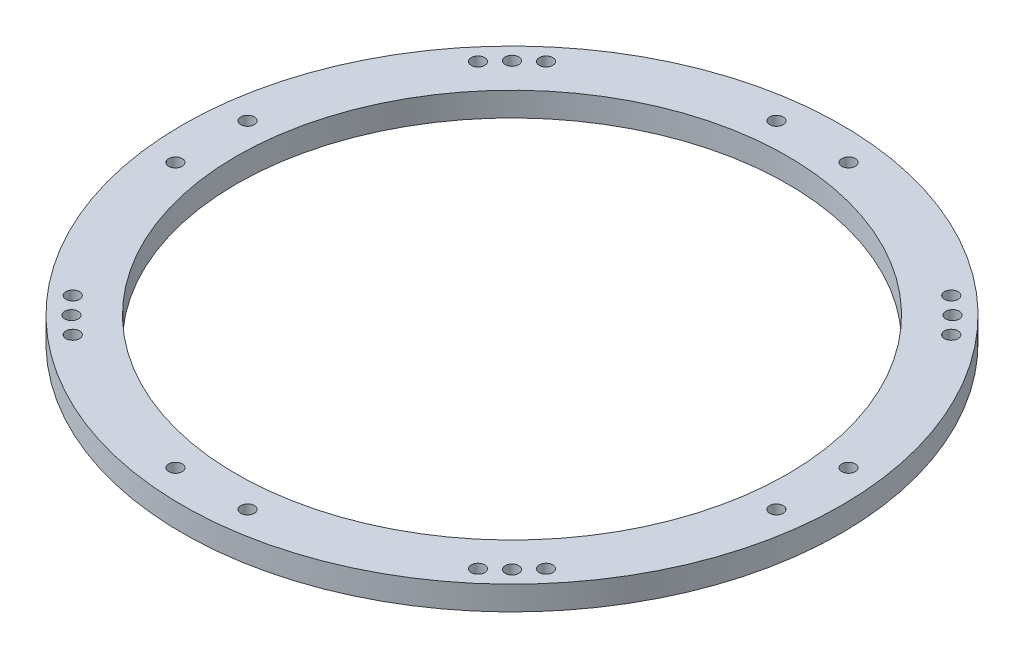
SolidWorks part; units mm, degrees
material "Oak"
ref_plane "Front Plane" through (0, 0, 0) normal (0, 0, 1) x (1, 0, 0)
ref_plane "Top Plane" through (0, 0, 0) normal (0, 1, 0) x (1, 0, 0)
ref_plane "Right Plane" through (0, 0, 0) normal (1, 0, 0) x (0, 0, -1)
sketch "Sketch1" plane through (0, 0, 0) normal (0, 0, 1) x (1, 0, 0)
  line L0 (0, -200000) -> (0, 218797.9879) construction
  line L5 (0, -200000) -> (0, 218797.9879) construction
  line L6 (174.1012, 207.3685) -> (174.1012, 194.6685)
  line L7 (145.5262, 207.3685) -> (174.1012, 207.3685)
  line L8 (174.1012, 194.6685) -> (145.5262, 194.6685)
  line L9 (145.5262, 194.6685) -> (145.5262, 207.3685)
revolve "Revolve1" add sketch "Sketch1" angle 360 about L5
hole_wizard "9/32 (0.28125) Diameter Hole1" positions "Sketch5" profile "Sketch6" hole size "9/32" standard "ANSI Inch" end condition through all
sketch "Sketch5" plane through (0, 207.3685, 0) normal (0, 1, 0) x (1, 0, 0)
  point P0 (-116.373, 116.373)
  point P3 (-107.0457, 125.0062)
  point P6 (-125.0062, 107.0457)
sketch "Sketch6" plane through (-116.373, 207.3685, -116.373) normal (1, 0, 0) x (0, 0, 1)
  line L0 (0, 0) -> (0, 12.7)
  line L1 (0, 12.7) -> (3.5719, 12.7)
  line L2 (3.5719, 12.7) -> (3.5719, 0)
  line L5 (3.5719, 0) -> (0, 0)
  line L11 (0, -6.35) -> (0, 107.95) construction
  dimension "Thru Hole Dia." = 7.1437
  dimension "Thru Hole Depth" = 12.7
sketch "Sketch7" plane through (0, 207.3685, 0) normal (0, 1, 0) x (1, 0, 0)
  line L0 (0, 0) -> (158.75, 0) construction
  line L1 (158.75, 19.05) -> (158.75, -19.05) construction
  circle A0 centre (158.75, -19.05) radius 3.5719
  circle A1 centre (158.75, 19.05) radius 3.5719
  point P6 (158.75, 0)
  dimension "D3" = 7.1437
  dimension "D1" = 38.1
  dimension "D2" = 158.75
extrude "Cut-Extrude1" cut sketch "Sketch7" against normal through all
pattern_circular "CirPattern1" count 4 over 360 about axis through (0, -200000, 0) along (0, -1, 0) of "9/32 (0.28125) Diameter Hole1", "Cut-Extrude1"
